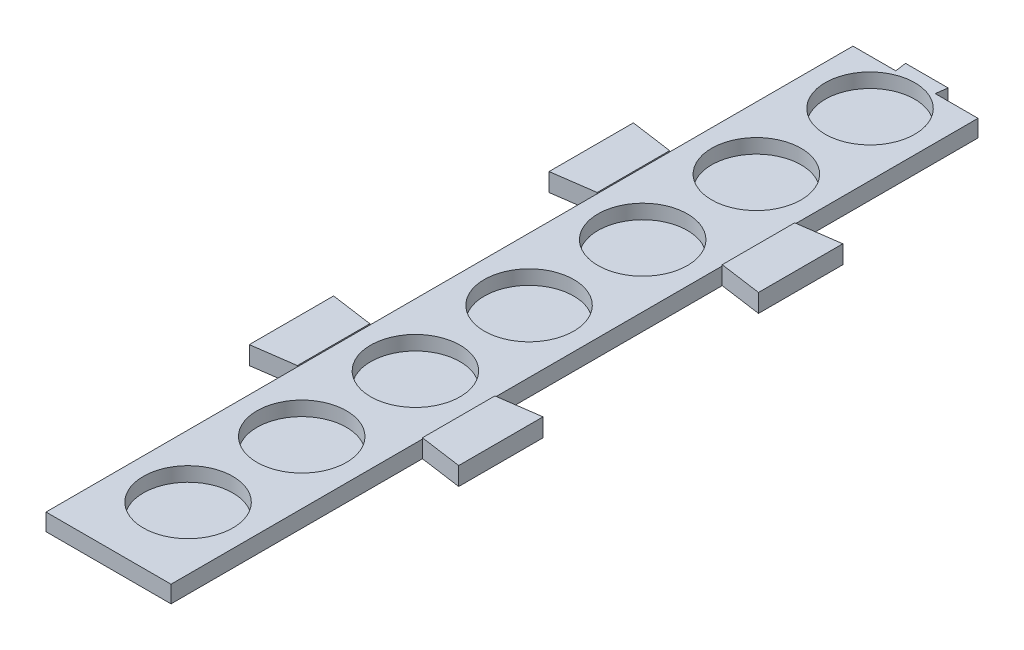
SolidWorks part; units mm, degrees
ref_plane "Front Plane" through (0, 0, 0) normal (0, 0, 1) x (1, 0, 0)
ref_plane "Top Plane" through (0, 0, 0) normal (0, 1, 0) x (1, 0, 0)
ref_plane "Right Plane" through (0, 0, 0) normal (1, 0, 0) x (0, 0, -1)
sketch "Sketch1" plane through (0, 0, 0) normal (0, 1, 0) x (1, 0, 0)
  line L1 (-13.97, -195.58) -> (13.97, -195.58)
  line L2 (-13.97, -195.58) -> (-13.97, 195.58)
  line L3 (-13.97, 195.58) -> (13.97, 195.58)
  line L4 (13.97, -195.58) -> (13.97, 195.58)
  line L5 (-13.97, -195.58) -> (13.97, 195.58) construction
  line L6 (-13.97, 195.58) -> (13.97, -195.58) construction
  point P0 (0, 0)
  dimension "D1" = 391.16
  dimension "D2" = 27.94
extrude "Boss-Extrude1" add sketch "Sketch1" along normal blind 3.81
sketch "Sketch2" plane through (0, 3.81, 0) normal (0, 1, 0) x (1, 0, 0)
  line L0 (-13.97, 195.58) -> (-13.97, -195.58) construction
  line L1 (13.97, 195.58) -> (-13.97, 195.58) construction
  line L3 (-13.97, -195.58) -> (13.97, -195.58) construction
  circle A0 centre (0, 177.8) radius 10
  circle A1 centre (0, 152.4) radius 10
  circle A2 centre (0, 127) radius 10
  circle A3 centre (0, 101.6) radius 10
  circle A4 centre (0, 76.2) radius 10
  circle A5 centre (0, 50.8) radius 10
  circle A6 centre (0, 25.4) radius 10
  circle A7 centre (0, 0) radius 10
  circle A8 centre (0, -25.4) radius 10
  circle A9 centre (0, -50.8) radius 10
  circle A10 centre (0, -76.2) radius 10
  circle A11 centre (0, -101.6) radius 10
  circle A12 centre (0, -127) radius 10
  circle A13 centre (0, -152.4) radius 10
  circle A14 centre (0, -177.8) radius 10
  dimension "D1" = 20
  dimension "D2" = 13.97
  dimension "D4" = 17.78
  dimension "D5" = 17.78
  dimension "D3" = 15
extrude "Cut-Extrude1" cut sketch "Sketch2" against normal blind 3.21
sketch "Sketch4" plane through (0, 0, 0) normal (0, 1, 0) x (1, 0, 0)
  line L0 (13.97, -56.2067) -> (23.4023, -54.881)
  line L2 (13.97, -195.58) -> (13.97, 195.58) construction
  line L5 (13.97, 144.78) -> (13.97, 128.5844)
  line L6 (0, 195.58) -> (0, -195.58) construction
  line L7 (13.97, 195.58) -> (-13.97, 195.58) construction
  line L8 (-13.97, -195.58) -> (13.97, -195.58) construction
  line L9 (13.97, -56.2067) -> (13.97, -72.4022)
  line L30 (-13.97, 144.78) -> (-13.97, 128.5844)
  line L31 (13.97, 144.78) -> (23.4023, 146.1056)
  line L32 (-13.97, 128.5844) -> (-23.4023, 127.2588)
  line L33 (13.97, 128.5844) -> (23.4023, 127.2588)
  line L34 (23.4023, 146.1056) -> (23.4023, 127.2588)
  line L35 (13.97, 144.78) -> (13.97, 128.5844)
  line L36 (13.97, 144.78) -> (13.97, 128.5844)
  line L37 (23.4023, 127.2588) -> (23.4023, 146.1056)
  line L38 (13.97, 144.78) -> (23.4023, 146.1056)
  line L39 (-13.97, 144.78) -> (-23.4023, 146.1056)
  line L40 (-23.4023, 127.2588) -> (-23.4023, 146.1056)
  line L41 (-23.4023, 146.1056) -> (-23.4023, 127.2588)
  line L42 (13.97, 77.7844) -> (23.4023, 79.1101)
  line L43 (13.97, 77.7844) -> (13.97, 61.5889)
  line L44 (13.97, 61.5889) -> (23.4023, 60.2633)
  line L45 (23.4023, 79.1101) -> (23.4023, 60.2633)
  line L46 (13.97, 10.7889) -> (23.4023, 12.1145)
  line L47 (13.97, 10.7889) -> (13.97, -5.4067)
  line L48 (13.97, -5.4067) -> (23.4023, -6.7323)
  line L49 (23.4023, 12.1145) -> (23.4023, -6.7323)
  line L50 (-13.97, 10.7889) -> (-13.97, -5.4067)
  line L51 (-13.97, -5.4067) -> (-23.4023, -6.7323)
  line L52 (-23.4023, 12.1145) -> (-23.4023, -6.7323)
  line L53 (-13.97, 10.7889) -> (-23.4023, 12.1145)
  line L54 (-13.97, 77.7844) -> (-13.97, 61.5889)
  line L55 (-13.97, 61.5889) -> (-23.4023, 60.2633)
  line L56 (-23.4023, 79.1101) -> (-23.4023, 60.2633)
  line L57 (-13.97, 77.7844) -> (-23.4023, 79.1101)
  line L58 (13.97, -72.4022) -> (23.4023, -73.7278)
  line L59 (23.4023, -54.881) -> (23.4023, -73.7278)
  line L60 (13.97, -123.2022) -> (23.4023, -121.8766)
  line L61 (13.97, -123.2022) -> (13.97, -139.3978)
  line L62 (13.97, -139.3978) -> (23.4023, -140.7234)
  line L63 (23.4023, -121.8766) -> (23.4023, -140.7234)
  line L72 (-13.97, -123.2022) -> (-13.97, -139.3978)
  line L73 (-13.97, -139.3978) -> (-23.4023, -140.7234)
  line L74 (-23.4023, -121.8766) -> (-23.4023, -140.7234)
  line L75 (-13.97, -123.2022) -> (-23.4023, -121.8766)
  line L76 (-13.97, -56.2067) -> (-13.97, -72.4022)
  line L77 (-13.97, -72.4022) -> (-23.4023, -73.7278)
  line L78 (-23.4023, -54.881) -> (-23.4023, -73.7278)
  line L79 (-13.97, -56.2067) -> (-23.4023, -54.881)
  line L80 (13.97, 144.78) -> (23.4023, 144.78) construction
  line L81 (13.97, 128.5844) -> (23.4023, 128.5844) construction
  dimension "D1" = 8
  dimension "D2" = 8
  dimension "D3" = 9.525
  dimension "D4" = 18.8468
  dimension "D5" = 50.8
  dimension "D6" = 5
  dimension "D7" = 50.8
extrude "Boss-Extrude2" add sketch "Sketch4" along normal blind 4.064 contours L54 L57 L56 L55 | L50 L53 L52 L51 | L49 L46 L47 L48 | L40 L32 L30 L39 | L34 L31 L5 L33 | L45 L44 L43 L42 | L76 L77 L78 L79 | L0 L59 L58 L9 | L60 L63 L62 L61 | L72 L73 L74 L75 region at (18.8051, 0, -136.6822) region at (-18.8051, 0, -136.6822) region at (18.8051, 0, -2.6911) region at (-18.8051, 0, -2.6911) region at (-18.8051, 0, -69.6867)
sketch "Sketch7" plane through (0, 0, -195.58) normal (0, 0, -1) x (-1, 0, 0)
  line L1 (-23.4023, 4.064) -> (23.4023, 4.064)
  line L2 (-23.4023, 4.064) -> (-23.4023, 0)
  line L3 (-23.4023, 0) -> (23.4023, 0)
  line L4 (23.4023, 4.064) -> (23.4023, 0)
extrude "Cut-Extrude2" cut sketch "Sketch7" against normal blind 210.82
sketch "Sketch8" plane through (0, 3.81, 0) normal (0, 1, 0) x (1, 0, 0)
  line L0 (-4.4055, -15.24) -> (-4.7625, -12.7)
  line L1 (-13.97, -15.24) -> (13.97, -15.24) construction
  line L2 (-4.7625, -12.7) -> (4.7625, -12.7)
  line L3 (4.7625, -12.7) -> (4.4055, -15.24)
  line L4 (4.4055, -15.24) -> (-4.4055, -15.24)
  line L5 (-4.4055, -15.24) -> (-4.4055, -12.7) construction
  line L6 (4.4055, -15.24) -> (4.4055, -12.7) construction
  dimension "D1" = 8
  dimension "D2" = 8
  dimension "D3" = 2.54
  dimension "D5" = 9.525
extrude "Boss-Extrude4" add sketch "Sketch8" against normal blind 4.064
sketch "Sketch9" plane through (0, 0, 15.24) normal (0, 0, -1) x (-1, 0, 0)
  line L0 (-23.4023, 4.064) -> (-23.4023, 0) construction
  line L2 (23.4023, 4.064) -> (23.4023, 0) construction
  line L3 (-13.97, 0) -> (-4.4055, 0) construction
  line L4 (4.4055, 0) -> (13.97, 0) construction
  circle A0 centre (7.5273, 2.032) radius 1.27
  circle A1 centre (-7.5273, 2.032) radius 1.27
  dimension "D3" = 2.54
  dimension "D4" = 2.54
  dimension "D1" = 15.875
  dimension "D2" = 15.875
  dimension "D5" = 2.032
  dimension "D6" = 2.032
